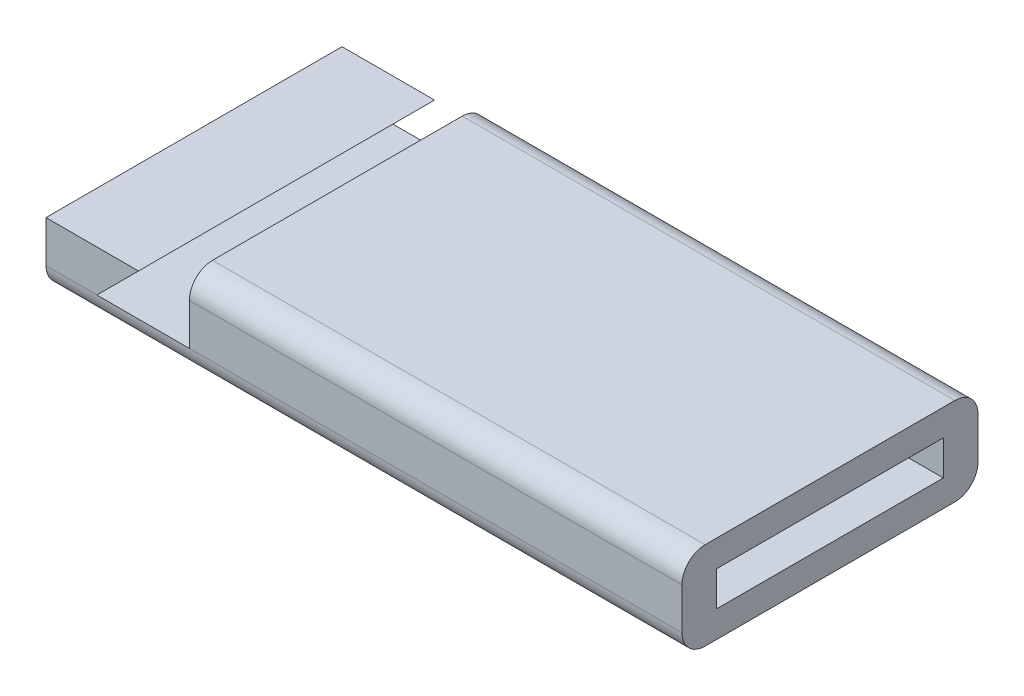
SolidWorks part; units mm, degrees
material "7079 Alloy"
ref_plane "Front Plane" through (0, 0, 0) normal (0, 0, 1) x (1, 0, 0)
ref_plane "Top Plane" through (0, 0, 0) normal (0, 1, 0) x (1, 0, 0)
ref_plane "Right Plane" through (0, 0, 0) normal (1, 0, 0) x (0, 0, -1)
sketch "Sketch1" plane through (0, 0, 0) normal (0, 1, 0) x (1, 0, 0)
  line L1 (0, 0) -> (55, 0)
  line L2 (0, 0) -> (0, 25.6)
  line L3 (0, 25.6) -> (55, 25.6)
  line L4 (55, 0) -> (55, 25.6)
  dimension "D1" = 55
  dimension "D2" = 25.6
extrude "Boss-Extrude1" add sketch "Sketch1" along normal blind 7.6
sketch "Sketch2" plane through (0, 0, -25.6) normal (0, 0, -1) x (-1, 0, 0)
  line L1 (-8, 5.6) -> (-4.4, 2)
  line L2 (-12.4, 7.6) -> (0, 7.6)
  line L3 (0, 5.6) -> (-8, 5.6)
  line L4 (-12.4, 2) -> (-4.4, 2)
  line L5 (-55, 0) -> (0, 0) construction
  line L8 (-12.4, 7.6) -> (-12.4, 2)
  line L11 (0, 7.6) -> (0, 5.6)
  line L12 (0, 5.6) -> (-8, 5.6)
  dimension "D1" = 8
  dimension "D2" = 8
  dimension "D3" = 45
  dimension "D4" = 2
  dimension "D5" = 2
extrude "Cut-Extrude1" cut sketch "Sketch2" against normal blind 25.6
fillet "Fillet1" radius 2 4 edges at (27.5, 0, -25.6) (27.5, 0, 0) (33.7, 7.6, -25.6) (33.7, 7.6, 0)
ref_plane "Plane1" through (0, 0, -12.8) normal (0, 0, -1) x (-1, 0, 0)
sketch "Sketch3" plane through (55, 0, 0) normal (1, 0, 0) x (0, 0, -1)
  line L1 (3, 5.3) -> (22.6, 5.3)
  line L2 (3, 5.3) -> (3, 2.3)
  line L3 (3, 2.3) -> (22.6, 2.3)
  line L4 (22.6, 5.3) -> (22.6, 2.3)
  line L6 (2, 7.6) -> (23.6, 7.6) construction
  line L7 (0, 5.6) -> (0, 2) construction
  line L8 (25.6, 5.6) -> (25.6, 2) construction
  dimension "D1" = 3
  dimension "D2" = 2.3
  dimension "D3" = 3
  dimension "D4" = 3
extrude "Cut-Extrude2" cut sketch "Sketch3" against normal blind 10
